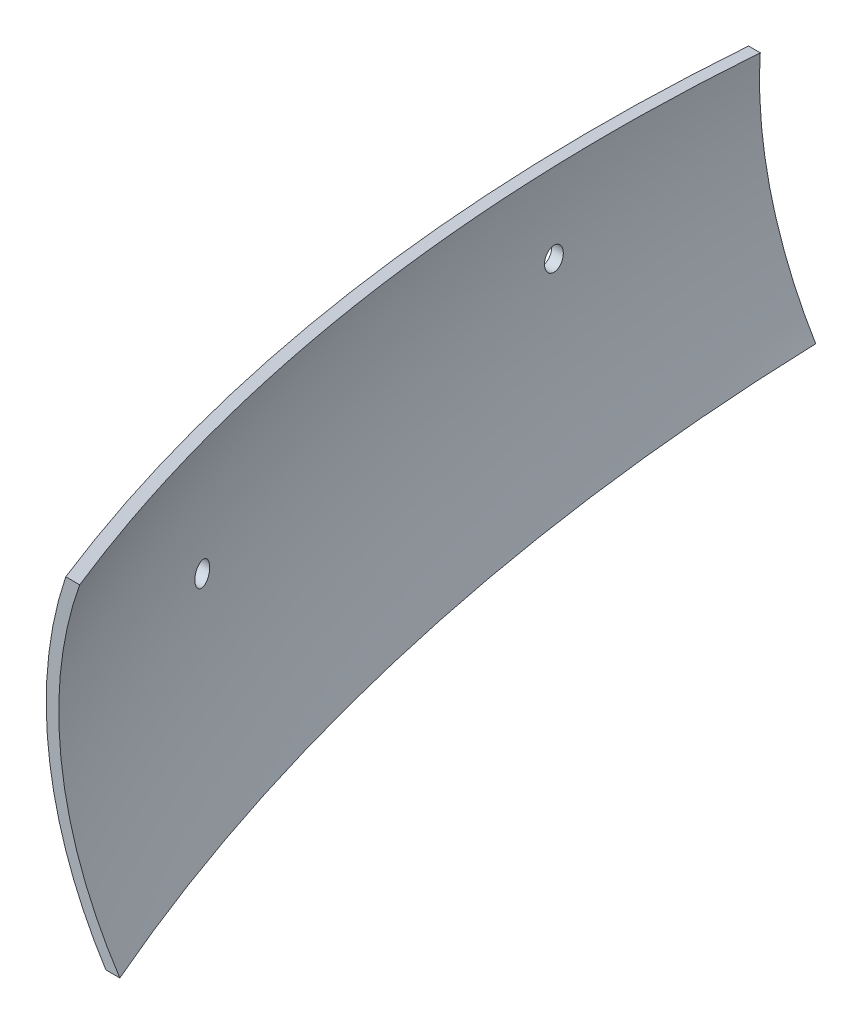
SolidWorks part; units mm, degrees
ref_plane "Front Plane" through (0, 0, 0) normal (0, 0, 1) x (1, 0, 0)
ref_plane "Top Plane" through (0, 0, 0) normal (0, 1, 0) x (1, 0, 0)
ref_plane "Right Plane" through (0, 0, 0) normal (1, 0, 0) x (0, 0, -1)
sketch "Sketch2" plane through (0, 0, 0) normal (0, 0, 1) x (1, 0, 0)
  line L0 (72.3704, 0) -> (82.3704, 0)
  line L1 (43.5787, 250) -> (53.5787, 250)
  arc A0 (72.3704, 0) -> (43.5787, 250) centre (340.9441, 157.5887) cw
  arc A1 (82.3704, 0) -> (53.5787, 250) centre (338.8585, 156.1968) cw
  dimension "D1" = 250
  dimension "D2" = 10
sketch "Shovel Curvature Axis" plane through (0, 0, 0) normal (0, 0, 1) x (1, 0, 0)
  line L0 (2000, -13.3717) -> (2000, 182.6602)
  line L1 (0, -403.9611) -> (0, 403.9611) construction
  dimension "D1" = 2000
revolve "Revolve1" add sketch "Sketch2" angle 88 about L0
sketch "Sketch5" plane through (0, 0, 0) normal (1, 0, 0) x (0, 0, -1)
  line L0 (-762.4592, 250) -> (-762.4592, 0)
  line L1 (-762.4592, 0) -> (-62.4592, 0)
  line L2 (-62.4592, 0) -> (-62.4592, 175)
  line L3 (-62.4592, 175) -> (-762.4592, 250)
  line L4 (0, 250) -> (-1945.2356, 250) construction
  line L5 (1046.9389, 0) -> (-1046.9389, 0) construction
  line L7 (-2824.2265, 1130.828) -> (2976.3022, 1130.828)
  line L8 (-2824.2265, 1130.828) -> (-2824.2265, -1305.0611)
  line L9 (-2824.2265, -1305.0611) -> (2976.3022, -1305.0611)
  line L10 (2976.3022, 1130.828) -> (2976.3022, -1305.0611)
  line L11 (-2824.2265, 1130.828) -> (2976.3022, -1305.0611) construction
  line L12 (-2824.2265, -1305.0611) -> (2976.3022, 1130.828) construction
  point P8 (76.0379, -87.1165)
  dimension "D1" = 700
  dimension "D2" = 175
extrude "Cut-Extrude2" cut sketch "Sketch5" against normal through all both and the other way through all
sketch "Sketch6" plane through (0, 0, 0) normal (1, 0, 0) x (0, 0, -1)
  line L0 (-587.4592, 130.34) -> (-237.4592, 130.34) construction
  line L1 (211.2744, 0) -> (-211.2744, 0) construction
  line L2 (-762.4592, 27.256) -> (-62.4592, 27.256) construction
  line L3 (-762.4592, 250) -> (-762.4592, 0) construction
  line L4 (-62.4592, 0) -> (-62.4592, 175) construction
  line L5 (-412.4592, 27.256) -> (-412.4592, 130.34) construction
  circle A0 centre (-587.4592, 130.34) radius 8.3125
  circle A1 centre (-237.4592, 130.34) radius 8.3125
  dimension "D3" = 16.625
  dimension "D1" = 130.34
  dimension "D2" = 350
extrude "Cut-Extrude4" cut sketch "Sketch6" along normal through all both
ref_plane "Locating Plane" through (30, 0, 0) normal (1, 0, 0) x (0, 0, -1)
equation "\"shovelWidth\"= 700"
equation "\"D1@Sketch5\"=\"shovelWidth\""
equation "\"holeDiameter\"= 5in / 8 + 0.75"
equation "\"D3@Sketch6\"=\"holeDiameter\""
